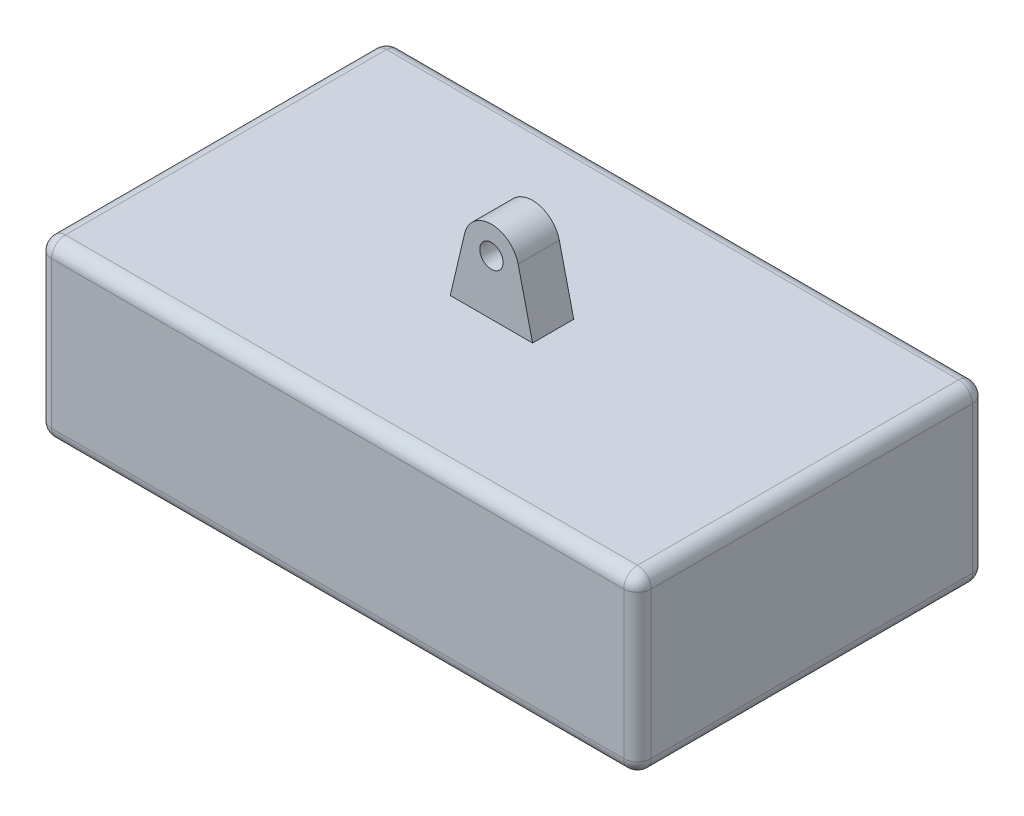
SolidWorks part; units mm, degrees
ref_plane "Front Plane" through (0, 0, 0) normal (0, 0, 1) x (1, 0, 0)
ref_plane "Top Plane" through (0, 0, 0) normal (0, 1, 0) x (1, 0, 0)
ref_plane "Right Plane" through (0, 0, 0) normal (1, 0, 0) x (0, 0, -1)
sketch "Sketch1" plane through (0, 0, 0) normal (0, 1, 0) x (1, 0, 0)
  line L1 (109.22, 63.5) -> (-109.22, 63.5)
  line L2 (109.22, 63.5) -> (109.22, -63.5)
  line L3 (109.22, -63.5) -> (-109.22, -63.5)
  line L4 (-109.22, 63.5) -> (-109.22, -63.5)
  line L5 (109.22, 63.5) -> (-109.22, -63.5) construction
  line L6 (109.22, -63.5) -> (-109.22, 63.5) construction
  point P0 (0, 0)
  dimension "D1" = 218.44
  dimension "D2" = 127
extrude "Boss-Extrude1" add sketch "Sketch1" along normal blind 63.5
sketch "Sketch2" plane through (0, 63.5, 0) normal (0, 1, 0) x (1, 0, 0)
  line L1 (-15, 7.5) -> (15, 7.5)
  line L2 (-15, 7.5) -> (-15, -7.5)
  line L3 (-15, -7.5) -> (15, -7.5)
  line L4 (15, 7.5) -> (15, -7.5)
  line L5 (-15, 7.5) -> (15, -7.5) construction
  line L6 (-15, -7.5) -> (15, 7.5) construction
  point P0 (0, 0)
  dimension "D1" = 15
  dimension "D2" = 30
extrude "Boss-Extrude2" add sketch "Sketch2" along normal blind 30
sketch "Sketch3" plane through (0, 0, -7.5) normal (0, 0, -1) x (-1, 0, 0)
  line L0 (0, 93.5) -> (0, 63.5) construction
  line L1 (-15, 93.5) -> (15, 93.5) construction
  line L2 (-109.22, 63.5) -> (109.22, 63.5) construction
  line L3 (-15, 63.5) -> (-9.7321, 85.7991)
  line L4 (15, 63.5) -> (9.7321, 85.7991)
  circle A0 centre (0, 83.5) radius 10
  circle A1 centre (0, 83.5) radius 4.25
  line M4 (15, 63.5) -> (15, 93.5)
  line M5 (15, 93.5) -> (-15, 93.5)
  line M6 (-15, 93.5) -> (-15, 63.5)
  dimension "D1" = 20
  dimension "D2" = 8.5
extrude "Cut-Extrude1" cut sketch "Sketch3" against normal up to next contours L0 A1 | A1 L0 | A0 L4 M4 M5 | A0 L3 M5 M6 region at (-12.0159, 84.3571, -7.5) region at (12.0159, 84.3571, -7.5) region at (-1.8038, 83.5, -7.5) region at (1.8038, 83.5, -7.5)
fillet "Fillet1" radius 5 12 edges at (0, 0, 63.5) (109.22, 0, 0) (0, 0, -63.5) (-109.22, 0, 0) (0, 63.5, 63.5) (109.22, 63.5, 0) (0, 63.5, -63.5) (-109.22, 63.5, 0) (109.22, 31.75, -63.5) (109.22, 31.75, 63.5) (-109.22, 31.75, 63.5) (-109.22, 31.75, -63.5)
